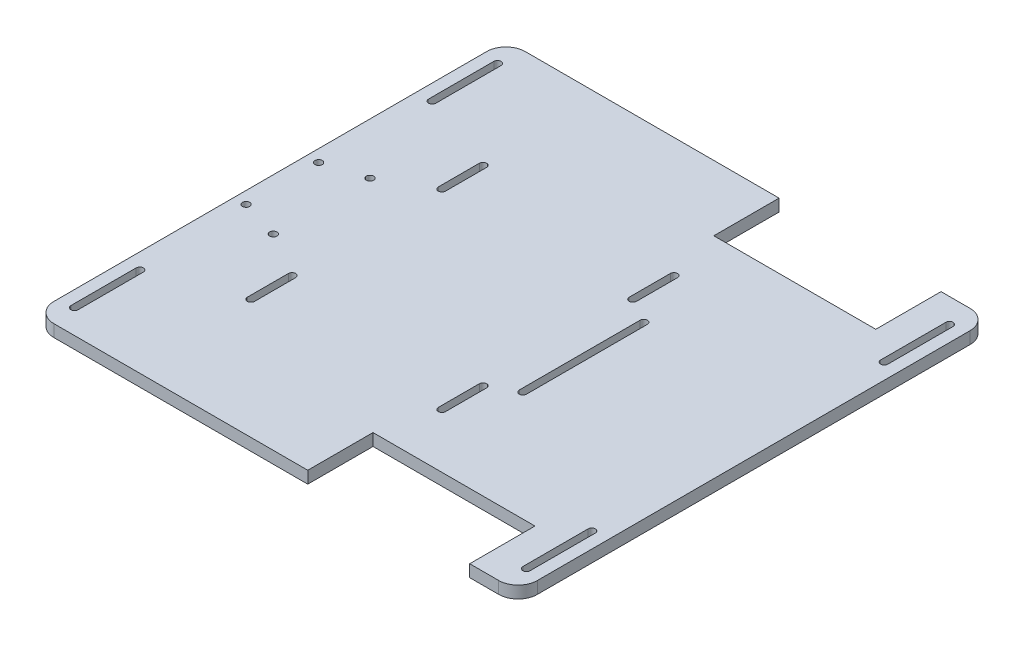
SolidWorks part; units mm, degrees
ref_plane "Front Plane" through (0, 0, 0) normal (0, 0, 1) x (1, 0, 0)
ref_plane "Top Plane" through (0, 0, 0) normal (0, 1, 0) x (1, 0, 0)
ref_plane "Right Plane" through (0, 0, 0) normal (1, 0, 0) x (0, 0, -1)
sketch "Sketch2" plane through (0, 0, 0) normal (0, 1, 0) x (1, 0, 0)
  line L1 (-100, -97.5) -> (100, -97.5)
  line L2 (-100, -97.5) -> (-100, 97.5)
  line L3 (-100, 97.5) -> (100, 97.5)
  line L4 (100, -97.5) -> (100, 97.5)
  line L5 (-100, -97.5) -> (100, 97.5) construction
  line L6 (-100, 97.5) -> (100, -97.5) construction
  point P0 (0, 0)
  dimension "D1" = 200
  dimension "D2" = 195
extrude "Boss-Extrude1" add sketch "Sketch2" along normal blind 5
sketch "Sketch3" plane through (0, 5, 0) normal (0, 1, 0) x (1, 0, 0)
  line L0 (-100, 0) -> (100, 0) construction
  line L1 (-100, 97.5) -> (-100, -97.5) construction
  line L2 (100, -97.5) -> (100, 97.5) construction
  line L3 (0, -97.5) -> (0, 97.5) construction
  line L4 (-100, -97.5) -> (100, -97.5) construction
  line L5 (100, 97.5) -> (-100, 97.5) construction
  line L6 (-93.5, -87.5) -> (-93.5, -60.5) construction
  line L7 (-95, -87.5) -> (-95, -60.5)
  line L8 (-92, -87.5) -> (-92, -60.5)
  line L9 (-93.5, 87.5) -> (-93.5, 60.5) construction
  line L10 (-95, 87.5) -> (-95, 60.5)
  line L11 (-92, 87.5) -> (-92, 60.5)
  line L12 (93.5, 87.5) -> (93.5, 60.5) construction
  line L13 (95, 87.5) -> (95, 60.5)
  line L14 (92, 87.5) -> (92, 60.5)
  line L15 (93.5, -87.5) -> (93.5, -60.5) construction
  line L16 (95, -87.5) -> (95, -60.5)
  line L17 (92, -87.5) -> (92, -60.5)
  arc A0 (-95, -87.5) -> (-92, -87.5) centre (-93.5, -87.5) ccw
  arc A1 (-92, -60.5) -> (-95, -60.5) centre (-93.5, -60.5) ccw
  arc A2 (-95, 87.5) -> (-92, 87.5) centre (-93.5, 87.5) cw
  arc A3 (-92, 60.5) -> (-95, 60.5) centre (-93.5, 60.5) cw
  arc A4 (95, 87.5) -> (92, 87.5) centre (93.5, 87.5) ccw
  arc A5 (92, 60.5) -> (95, 60.5) centre (93.5, 60.5) ccw
  arc A6 (95, -87.5) -> (92, -87.5) centre (93.5, -87.5) cw
  arc A7 (92, -60.5) -> (95, -60.5) centre (93.5, -60.5) cw
  point P14 (-93.5, -74)
  point P21 (-93.5, 74)
  point P28 (93.5, 74)
  point P35 (93.5, -74)
  dimension "D2" = 1.5
  dimension "D3" = 5
  dimension "D4" = 10
  dimension "D1" = 27
extrude "Cut-Extrude1" cut sketch "Sketch3" against normal through all
sketch "Sketch4" plane through (0, 0, 0) normal (0, -1, 0) x (1, 0, 0)
  line L0 (-100, 0) -> (100, 0) construction
  line L1 (-100, -97.5) -> (-100, 97.5) construction
  line L2 (100, 97.5) -> (100, -97.5) construction
  line L3 (100, -97.5) -> (-100, -97.5) construction
  line L4 (13, -97.5) -> (80, -97.5)
  line L5 (13, -97.5) -> (13, -70.5)
  line L6 (13, -70.5) -> (80, -70.5)
  line L7 (80, -97.5) -> (80, -70.5)
  line L8 (80, 97.5) -> (80, 70.5)
  line L9 (13, 97.5) -> (80, 97.5)
  line L10 (13, 70.5) -> (80, 70.5)
  line L11 (13, 97.5) -> (13, 70.5)
  dimension "D1" = 27
  dimension "D2" = 67
  dimension "D3" = 20
extrude "Cut-Extrude2" cut sketch "Sketch4" against normal through all
sketch "Sketch5" plane through (0, 0, 0) normal (0, -1, 0) x (1, 0, 0)
  line L0 (-100, 0) -> (100, 0) construction
  line L1 (-100, -97.5) -> (-100, 97.5) construction
  line L2 (100, 97.5) -> (100, -97.5) construction
  line L3 (13, -70.5) -> (13, -97.5) construction
  line L4 (23, -52) -> (-64, -52)
  line L5 (23, -52) -> (23, 52)
  line L6 (23, 52) -> (-64, 52)
  line L7 (-64, -52) -> (-64, 52)
  line L8 (23, -52) -> (-64, 52) construction
  line L9 (23, 52) -> (-64, -52) construction
  line L10 (-60, -48) -> (-60, -31) construction
  line L11 (-61.5, -48) -> (-61.5, -31)
  line L12 (-58.5, -48) -> (-58.5, -31)
  line L13 (-60, 48) -> (-60, 31) construction
  line L14 (-61.5, 48) -> (-61.5, 31)
  line L15 (-58.5, 48) -> (-58.5, 31)
  line L16 (-20.5, -52) -> (-20.5, 52) construction
  line L17 (19, 48) -> (19, 31) construction
  line L18 (20.5, 48) -> (20.5, 31)
  line L19 (17.5, 48) -> (17.5, 31)
  line L20 (19, -48) -> (19, -31) construction
  line L21 (20.5, -48) -> (20.5, -31)
  line L22 (17.5, -48) -> (17.5, -31)
  arc A0 (-61.5, -48) -> (-58.5, -48) centre (-60, -48) ccw
  arc A1 (-58.5, -31) -> (-61.5, -31) centre (-60, -31) ccw
  arc A2 (-61.5, 48) -> (-58.5, 48) centre (-60, 48) cw
  arc A3 (-58.5, 31) -> (-61.5, 31) centre (-60, 31) cw
  arc A4 (20.5, 48) -> (17.5, 48) centre (19, 48) ccw
  arc A5 (17.5, 31) -> (20.5, 31) centre (19, 31) ccw
  arc A6 (20.5, -48) -> (17.5, -48) centre (19, -48) cw
  arc A7 (17.5, -31) -> (20.5, -31) centre (19, -31) cw
  point P6 (-20.5, 0)
  point P15 (-60, -39.5)
  point P22 (-60, 39.5)
  point P31 (19, 39.5)
  point P38 (19, -39.5)
  dimension "D5" = 1.5
  dimension "D1" = 104
  dimension "D2" = 87
  dimension "D3" = 10
  dimension "D4" = 17
  dimension "D6" = 2.5
  dimension "D7" = 4
extrude "Cut-Extrude4" cut sketch "Sketch5" against normal through all contours L11 A1 L12 A0 | L14 A3 L15 A2 | L19 A5 L18 A4 | L22 A7 L21 A6
sketch "Sketch7" plane through (0, 0, 0) normal (0, -1, 0) x (1, 0, 0)
  line L0 (29.5, -25) -> (29.5, 25) construction
  line L1 (-100, 0) -> (100, 0) construction
  line L2 (28, -25) -> (28, 25)
  line L3 (31, -25) -> (31, 25)
  line L4 (23, -52) -> (23, 52) construction
  arc A0 (28, -25) -> (31, -25) centre (29.5, -25) ccw
  arc A1 (31, 25) -> (28, 25) centre (29.5, 25) ccw
  point P4 (29.5, 0)
  dimension "D2" = 1.5
  dimension "D1" = 50
  dimension "D3" = 5
extrude "Cut-Extrude5" cut sketch "Sketch7" against normal through all
sketch "Sketch8" plane through (0, 5, 0) normal (0, 1, 0) x (1, 0, 0)
  line L0 (-100, 0) -> (100, 0) construction
  line L1 (-100, 97.5) -> (-100, -97.5) construction
  line L2 (100, -97.5) -> (100, 97.5) construction
  line L3 (-78.75, -25) -> (-78.75, 25) construction
  line L4 (-95, -25) -> (-62.5, -25)
  line L5 (-95, -25) -> (-95, 25)
  line L6 (-95, 25) -> (-62.5, 25)
  line L7 (-62.5, -25) -> (-62.5, 25)
  line L8 (-95, -25) -> (-62.5, 25) construction
  line L9 (-95, 25) -> (-62.5, -25) construction
  circle A0 centre (-78.75, -19.995) radius 1.5
  circle A1 centre (-78.75, 19.995) radius 1.5
  point P6 (-78.75, 0)
  dimension "D4" = 3
  dimension "D1" = 32.5
  dimension "D2" = 50
  dimension "D3" = 5
  dimension "D5" = 39.99
extrude "Cut-Extrude6" cut sketch "Sketch8" against normal through all contours A1 | A0 region at (-78.75, 5, -19.995)
sketch "Sketch9" plane through (0, 5, 0) normal (0, 1, 0) x (1, 0, 0)
  line L0 (-100, 0) -> (100, 0) construction
  line L1 (-100, 97.5) -> (-100, -97.5) construction
  line L2 (100, -97.5) -> (100, 97.5) construction
  line L4 (-100, -25) -> (-90, -25)
  line L5 (-100, -25) -> (-100, 25)
  line L6 (-100, 25) -> (-90, 25)
  line L7 (-90, -25) -> (-90, 25)
  line L8 (-100, -25) -> (-90, 25) construction
  line L9 (-100, 25) -> (-90, -25) construction
  circle A0 centre (-95, 15) radius 1.5
  circle A1 centre (-95, -15) radius 1.5
  point P6 (-95, 0)
  dimension "D4" = 3
  dimension "D1" = 10
  dimension "D2" = 0
  dimension "D3" = 50
  dimension "D5" = 30
  dimension "D6" = 5
extrude "Cut-Extrude7" cut sketch "Sketch9" against normal through all contours A0 | A1
fillet "Fillet1" radius 8 4 edges at (100, 2.5, -97.5) (100, 2.5, 97.5) (-100, 2.5, -97.5) (-100, 2.5, 97.5)
